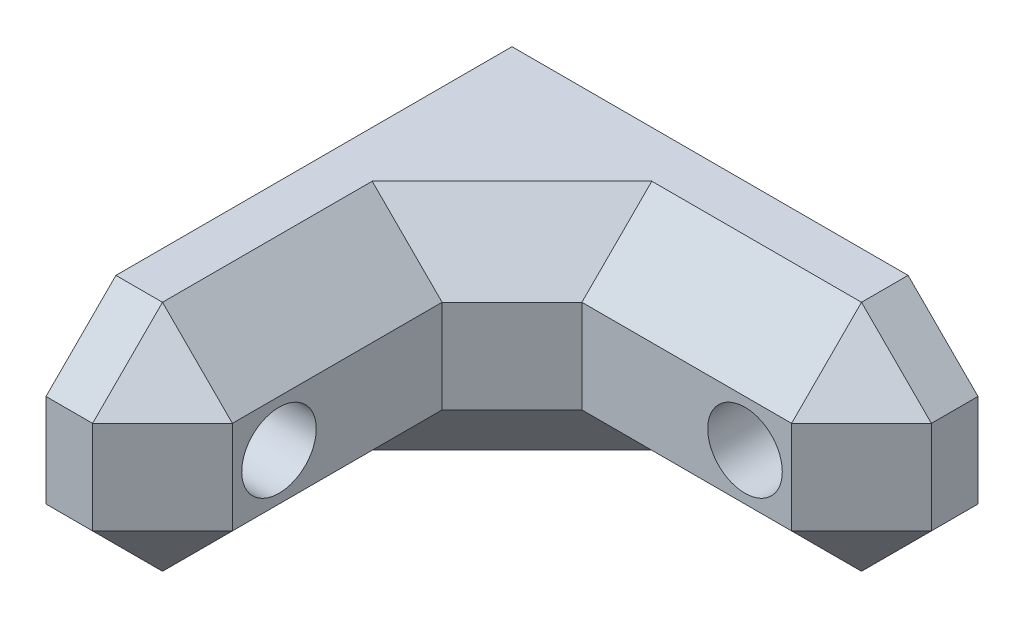
SolidWorks part; units mm, degrees
ref_plane "Ebene vorne" through (0, 0, 0) normal (0, 0, 1) x (1, 0, 0)
ref_plane "Ebene oben" through (0, 0, 0) normal (0, 1, 0) x (1, 0, 0)
ref_plane "Ebene rechts" through (0, 0, 0) normal (1, 0, 0) x (0, 0, -1)
sketch "Skizze1" plane through (0, 0, 0) normal (0, 0, 1) x (1, 0, 0)
  line L0 (5, 10) -> (5, 0)
  line L1 (0, 0) -> (20, 0)
  line L2 (0, 0) -> (0, 10)
  line L3 (0, 10) -> (20, 10)
  line L4 (20, 0) -> (20, 10)
  circle A0 centre (15, 5) radius 1.6
extrude "Aufsatz-Linear austragen1" add sketch "Skizze1" along normal blind 5 contours L1 L4 L3 L0 A0 region at (12.3584, 5, 0)
extrude "Aufsatz-Linear austragen2" add sketch "Skizze1<9>" along normal blind 20 contours L3 L2 L1 L0 region at (2.5, 5, 0)
sketch "Skizze1<9>" plane through (0, 0, 0) normal (0, 0, 1) x (1, 0, 0) same geometry as "Skizze1"
sketch "Skizze3" plane through (5, 0, 0) normal (1, 0, 0) x (0, 0, -1)
  circle A0 centre (-15, 5) radius 1.6
extrude "Schnitt-Linear austragen2" cut sketch "Skizze3" against normal blind 20
chamfer "Fase1" distance 3 angle 45 11 edges at (20, 10, 2.5) (20, 0, 2.5) (2.5, 0, 20) (2.5, 10, 20) (5, 5, 20) (20, 5, 5)
